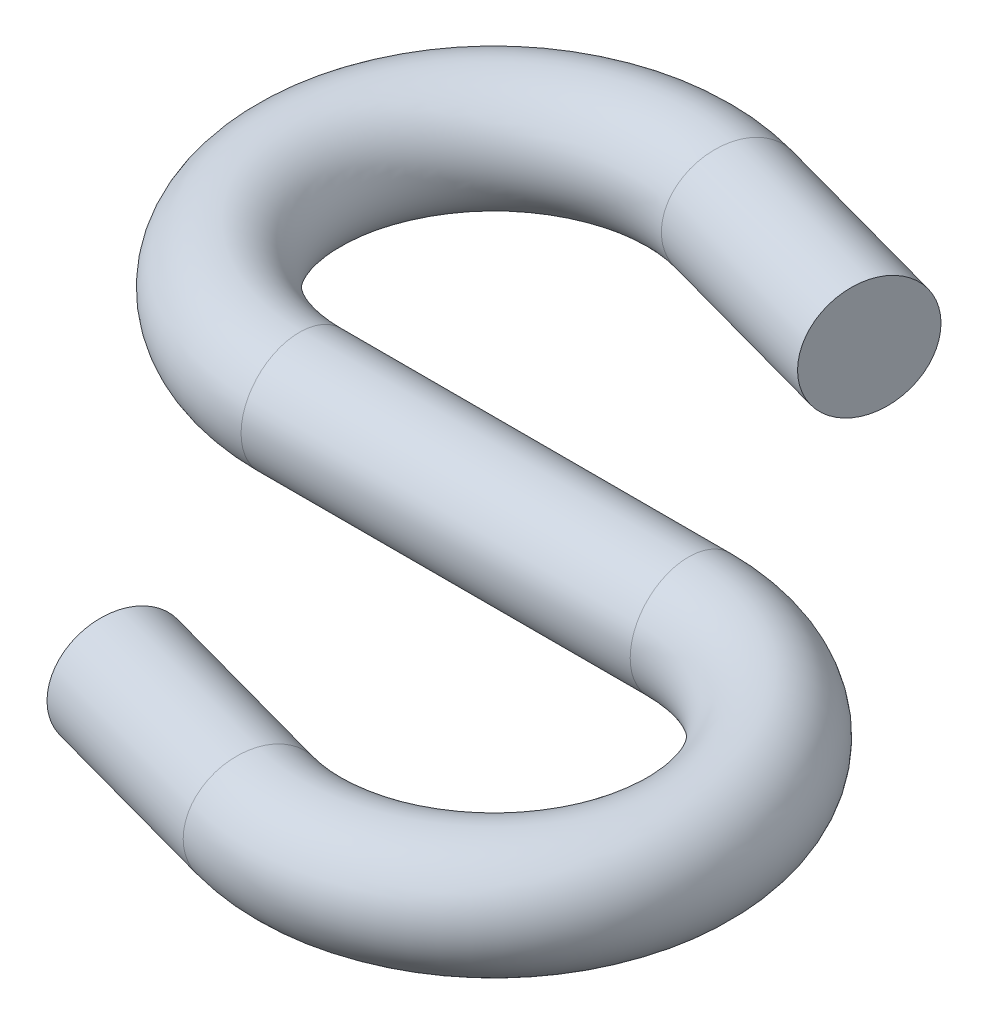
SolidWorks part; units mm, degrees
material "Plain Carbon Steel"
ref_plane "Front Plane" through (0, 0, 0) normal (0, 0, 1) x (1, 0, 0)
ref_plane "Top Plane" through (0, 0, 0) normal (0, 1, 0) x (1, 0, 0)
ref_plane "Right Plane" through (0, 0, 0) normal (1, 0, 0) x (0, 0, -1)
sketch "Sketch1" plane through (0, 0, 0) normal (0, 1, 0) x (1, 0, 0)
  line L0 (0, 0) -> (-15.875, 0)
  line L1 (-11.6775, 31.185) -> (3.6325, 26.9875)
  line L2 (-15.875, 15.875) -> (0, 0) construction
  arc A0 (-15.875, 0) -> (-11.6775, 31.185) centre (-15.875, 15.875) cw
  dimension "D1" = 15.875
  dimension "D2" = 26.9875
  dimension "D3" = 45
ref_axis "Axis1" through (0, 55, 0) along (0, -1, 0)
sketch "Sketch2" plane through (0, 0, 0) normal (1, 0, 0) x (0, 0, -1)
  circle A0 centre (0, 0) radius 4.7625
  dimension "D1" = 9.525
sweep "Sweep1" add profiles "Sketch2" path "Sketch1"
pattern_circular "CirPattern1" count 2 over 360 about axis through (0, 55, 0) along (0, -1, 0) of "Sweep1"
ref_plane "Plane1" through (0, 0, 0) normal (-0.7071, 0, 0.7071) x (0.7071, 0, 0.7071)
